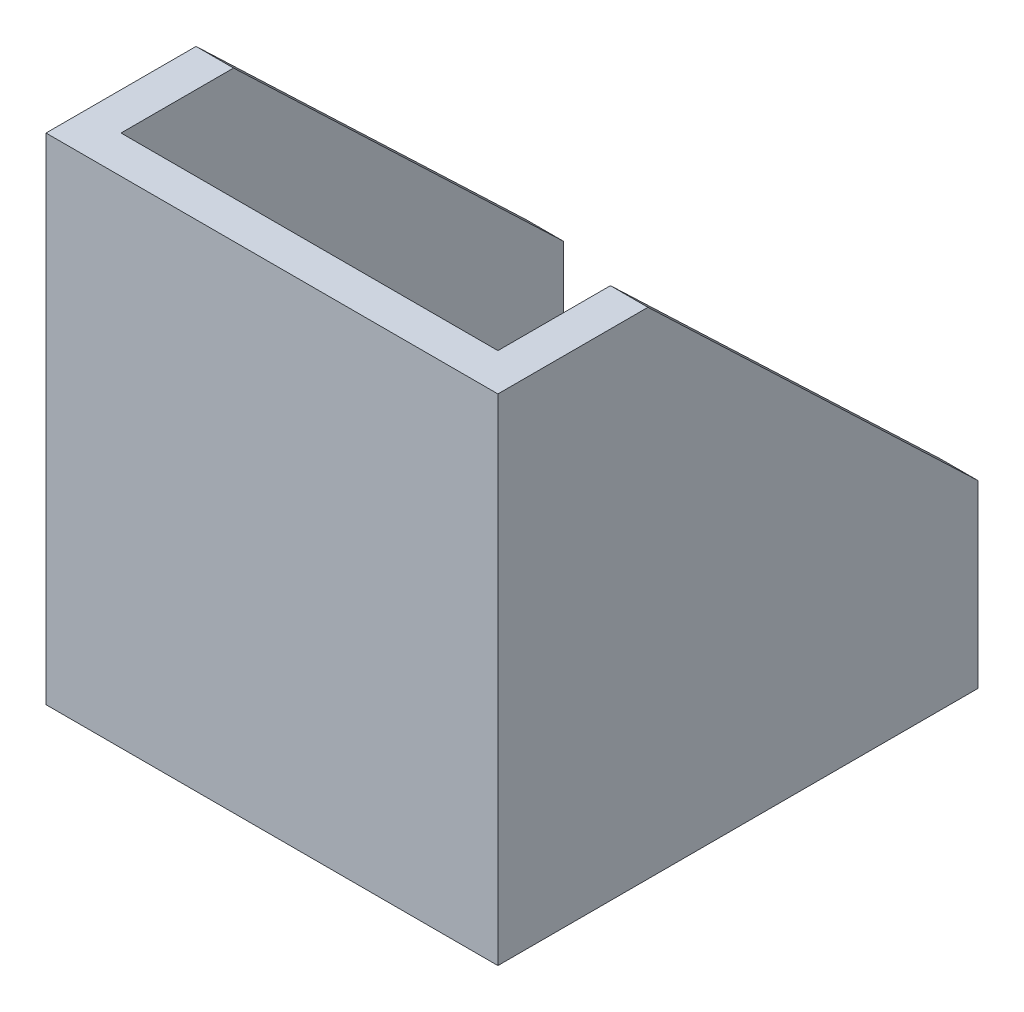
SolidWorks part; units mm, degrees
ref_plane "Front Plane" through (0, 0, 0) normal (0, 0, 1) x (1, 0, 0)
ref_plane "Top Plane" through (0, 0, 0) normal (0, 1, 0) x (1, 0, 0)
ref_plane "Right Plane" through (0, 0, 0) normal (1, 0, 0) x (0, 0, -1)
sketch "Sketch2" plane through (0, 0, 0) normal (0, 1, 0) x (1, 0, 0)
  line L0 (15.061, 0) -> (15.061, 32)
  line L1 (-12.561, 2.5) -> (12.561, 2.5)
  line L2 (-12.561, 2.5) -> (-12.561, 32)
  line L4 (12.561, 2.5) -> (12.561, 32)
  line L5 (15.061, 32) -> (12.561, 32)
  line L7 (-15.061, 32) -> (-15.061, 0)
  line L8 (-15.061, 0) -> (15.061, 0)
  line L10 (-15.061, 32) -> (-12.561, 32)
  point P4 (0, 2.5)
  point P12 (0, 0)
  dimension "D1" = 2.5
  dimension "D2" = 2.5
  dimension "D3" = 29.5
  dimension "D4" = 25.122
extrude "Boss-Extrude1" add sketch "Sketch2" along normal blind 31
sketch "Sketch3" plane through (15.061, 0, 0) normal (1, 0, 0) x (0, 0, -1)
  line L0 (32, 10) -> (10, 31)
  line L3 (10, 31) -> (32, 31)
  line L4 (32, 31) -> (32, 10)
  line L5 (0, 55) -> (0, -55) construction
  line L6 (32, 31) -> (32, 0) construction
  line L7 (0, 0) -> (32, 0) construction
  line L8 (0, 31) -> (32, 31) construction
  point P2 (47.9, 10.6856)
  point P4 (10, 31)
  dimension "D1" = 10
  dimension "D2" = 10
extrude "Cut-Extrude1" cut sketch "Sketch3" against normal through all
sketch "Sketch4" plane through (0, 0, 0) normal (0, -1, 0) x (1, 0, 0)
  line L0 (-15.061, 0) -> (-15.061, -32)
  line L2 (-15.061, -32) -> (-10.061, -32)
  line L4 (-7.3658, -6) -> (7.3658, -6)
  line L6 (10.061, -32) -> (15.061, -32)
  line L8 (15.061, -32) -> (15.061, 0)
  line L9 (15.061, 0) -> (-15.061, 0)
  line L10 (15.061, 0) -> (15.061, -32) construction
  line L13 (-12.561, -2.5) -> (-12.561, -32) construction
  line L18 (-12.561, -10) -> (-9.9639, -7.5)
  line L20 (-12.561, -10) -> (-12.561, -20)
  line L21 (-12.561, -20) -> (-7.061, -29)
  line L23 (12.561, -32) -> (12.561, -2.5) construction
  line L24 (12.561, -10) -> (12.561, -20)
  line L25 (12.561, -20) -> (7.061, -29)
  line L26 (12.561, -10) -> (8.1492, -6.1041)
  line L27 (12.561, -2.5) -> (-12.561, -2.5) construction
  arc A0 (7.061, -29) -> (10.061, -32) centre (10.061, -29) ccw
  arc A1 (-10.061, -32) -> (-7.061, -29) centre (-10.061, -29) ccw
  circle A2 centre (-10.2499, -4.95) radius 1.05
  circle A3 centre (-10.2499, -29.4) radius 1.05
  circle A4 centre (10.2499, -29.4) radius 1.05
  circle A5 centre (10.2499, -4.95) radius 1.05
  arc A6 (7.3658, -6) -> (8.1492, -6.1041) centre (7.3658, -9) cw
  arc A7 (-9.9639, -7.5) -> (-7.3658, -6) centre (-7.3658, -9) cw
  point P17 (7.061, -32)
  point P20 (-7.061, -32)
  point P29 (0, 0)
  point P31 (0, 0)
  dimension "D4" = 3
  dimension "D5" = 2.1
  dimension "D10" = 3
  dimension "D11" = 10
  dimension "D17" = 5
  dimension "D1" = 8
  dimension "D2" = 6
  dimension "D3" = 32
  dimension "D6" = 4.8111
  dimension "D7" = 4.95
  dimension "D8" = 4.8111
  dimension "D9" = 29.4
  dimension "D12" = 20
  dimension "D13" = 8
  dimension "D14" = 5
  dimension "D15" = 8
  dimension "D16" = 20.122
extrude "Boss-Extrude2" add sketch "Sketch4" along normal blind 2
